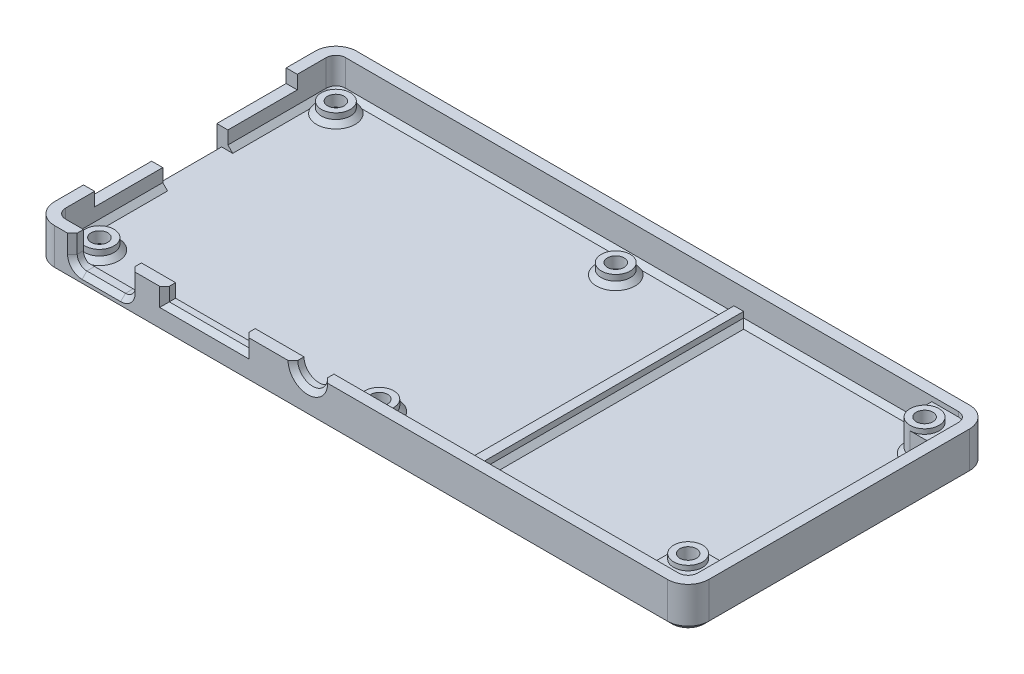
SolidWorks part; units mm, degrees
ref_plane "Front Plane" through (0, 0, 0) normal (0, 0, 1) x (1, 0, 0)
ref_plane "Top Plane" through (0, 0, 0) normal (0, 1, 0) x (1, 0, 0)
ref_plane "Right Plane" through (0, 0, 0) normal (1, 0, 0) x (0, 0, -1)
sketch "Sketch1" plane through (0, 0, 0) normal (0, 1, 0) x (1, 0, 0)
  line L0 (-71.5618, 3.106) -> (57.4382, 3.106) construction
  line L1 (-71.5618, 31.106) -> (57.4382, 31.106)
  line L2 (-71.5618, 31.106) -> (-71.5618, -24.894)
  line L3 (-71.5618, -24.894) -> (57.4382, -24.894)
  line L4 (57.4382, 31.106) -> (57.4382, -24.894)
  line L5 (-60.6618, -24.894) -> (-60.6618, -31.6828) construction
  line L6 (-68.0618, 27.606) -> (-10.0618, 27.606)
  line L7 (-68.0618, 27.606) -> (-68.0618, -21.394)
  line L8 (-68.0618, -21.394) -> (-10.0618, -21.394)
  line L9 (-10.0618, 27.606) -> (-10.0618, -21.394)
  line L10 (-39.5618, -24.894) -> (-39.5618, -31.6828) construction
  line L11 (-18.0618, -24.894) -> (-18.0618, -31.6828) construction
  line L12 (-65.4118, -26.5648) -> (-55.9118, -26.5648) construction
  line L13 (-48.0618, -26.5648) -> (-31.0618, -26.5648) construction
  line L14 (-22.0618, -26.5648) -> (-14.0618, -26.5648) construction
  line L15 (-72.5618, 9.606) -> (-72.5618, -3.394) construction
  line L16 (-71.5618, 3.106) -> (-72.5618, 3.106) construction
  dimension "D1" = 129
  dimension "D2" = 56
  dimension "D3" = 49
  dimension "D4" = 58
  dimension "D5" = 3.5
  dimension "D6" = 3.5
  dimension "D7" = 10.9
  dimension "D8" = 32
  dimension "D9" = 53.5
  dimension "D10" = 2
  dimension "D11" = 13
  dimension "D12" = 9.5
  dimension "D13" = 17
  dimension "D14" = 8
sketch "Sketch3" plane through (0, 0, 0) normal (0, 1, 0) x (1, 0, 0)
  line L4 (60.7382, 34.406) -> (-74.8618, 34.406)
  line L5 (-74.8618, 34.406) -> (-74.8618, -28.194)
  line L6 (-74.8618, -28.194) -> (60.7382, -28.194)
  line L7 (60.7382, -28.194) -> (60.7382, 34.406)
  line L8 (58.4382, 32.106) -> (-72.5618, 32.106)
  line L9 (58.4382, -25.894) -> (58.4382, 32.106)
  line L10 (-72.5618, -25.894) -> (58.4382, -25.894)
  line L11 (-72.5618, 32.106) -> (-72.5618, -25.894)
  line L12 (58.4382, 32.106) -> (-72.5618, 32.106)
  line L13 (58.4382, -25.894) -> (58.4382, 32.106)
  line L14 (-72.5618, -25.894) -> (58.4382, -25.894)
  line L15 (-72.5618, 32.106) -> (-72.5618, -25.894)
  line L16 (-7.0618, 3.106) -> (-7.0618, 34.406) construction
  line L17 (-71.5618, 3.106) -> (57.4382, 3.106) construction
  line L20 (-74.8618, 3.106) -> (52.7382, 3.106) construction
  line L25 (60.7382, -28.194) -> (60.7382, 34.406) construction
  line L26 (58.4382, -25.894) -> (58.4382, 32.106) construction
  dimension "D1" = 1
  dimension "D2" = 2.3
extrude "Boss-Extrude1" add sketch "Sketch3" along normal blind 8.5
sketch "Sketch5" plane through (0, 0, 0) normal (0, 1, 0) x (1, 0, 0)
  line L1 (-72.5618, 32.106) -> (58.4382, 32.106)
  line L2 (-72.5618, 32.106) -> (-72.5618, -25.894)
  line L3 (-72.5618, -25.894) -> (58.4382, -25.894)
  line L4 (58.4382, 32.106) -> (58.4382, -25.894)
extrude "Boss-Extrude2" add sketch "Sketch5" along normal blind 2
sketch "Sketch6" plane through (0, 2, 0) normal (0, 1, 0) x (1, 0, 0)
  circle A0 centre (-68.0618, 27.606) radius 3
  circle A1 centre (-68.0618, -21.394) radius 3
  circle A2 centre (-10.0618, -21.394) radius 3
  circle A3 centre (-10.0618, 27.606) radius 3
extrude "Boss-Extrude3" add sketch "Sketch6" along normal blind 2.2
sketch "Sketch10" plane through (0, 2, 0) normal (0, 1, 0) x (1, 0, 0)
  line L0 (58.4382, 32.106) -> (-72.5618, 32.106) construction
  line L1 (9.9382, 32.106) -> (11.9382, 32.106)
  line L2 (9.9382, 32.106) -> (9.9382, -25.894)
  line L3 (9.9382, -25.894) -> (11.9382, -25.894)
  line L4 (11.9382, 32.106) -> (11.9382, -25.894)
  line L5 (-72.5618, -25.894) -> (58.4382, -25.894) construction
  line L6 (-10.0618, 27.606) -> (-10.0618, -21.394) construction
  dimension "D1" = 2
  dimension "D2" = 20
extrude "Boss-Extrude4" add sketch "Sketch10" along normal blind 2.2
sketch "Sketch11" plane through (0, 0, 28.194) normal (0, 0, 1) x (1, 0, 0)
  line L0 (-74.8618, 8.5) -> (-74.8618, 0) construction
  line L1 (-66.8618, 8.5) -> (-54.8618, 8.5)
  line L2 (-66.8618, 8.5) -> (-66.8618, 2.7)
  line L3 (-66.8618, 2.7) -> (-54.8618, 2.7)
  line L4 (-54.8618, 8.5) -> (-54.8618, 2.7)
  line L5 (-74.8618, 0) -> (60.7382, 0) construction
  line L6 (-60.8618, 8.5) -> (-60.6618, 0) construction
  line L7 (-65.4118, 0) -> (-55.9118, 0) construction
  line L9 (-47.778, 8.5) -> (-31.278, 8.5)
  line L10 (-47.778, 8.5) -> (-47.778, 5.7)
  line L11 (-47.778, 5.7) -> (-31.278, 5.7)
  line L12 (-31.278, 8.5) -> (-31.278, 5.7)
  line L13 (-68.0618, 0) -> (-10.0618, 0) construction
  line L14 (-39.5618, 0) -> (-39.528, 8.5) construction
  line L15 (-48.0618, 0) -> (-31.0618, 0) construction
  line L16 (-18.0618, 0) -> (-18.0618, 8.5) construction
  line L17 (-22.0618, 0) -> (-14.0618, 0) construction
  line L18 (-74.8618, 8.5) -> (60.7382, 8.5) construction
  circle A0 centre (-18.0618, 8.5) radius 3.1
  dimension "D5" = 6.2
  dimension "D1" = 2.7
  dimension "D2" = 12
  dimension "D3" = 5.7
  dimension "D4" = 16.5
  dimension "D6" = 8
  dimension "D7" = 5.8
  dimension "D8" = 2.8
extrude "Cut-Extrude1" cut sketch "Sketch11" against normal up to next
sketch "Sketch12" plane through (-74.8618, 0, 0) normal (-1, 0, 0) x (0, 0, 1)
  line L0 (-3.106, 0) -> (-3.106, 8.5) construction
  line L1 (-27.606, 0) -> (21.394, 0) construction
  line L2 (-34.406, 8.5) -> (28.194, 8.5) construction
  line L3 (-24.106, 5.7) -> (17.894, 5.7)
  line L4 (-9.7329, 5.7) -> (3.7671, 5.7)
  line L5 (-9.7329, 5.7) -> (-9.7329, 2)
  line L6 (-9.7329, 2) -> (3.7671, 2)
  line L7 (3.7671, 5.7) -> (3.7671, 2)
  line L8 (-24.106, 8.5) -> (17.894, 8.5)
  line L9 (-24.106, 8.5) -> (-24.106, 5.7)
  line L11 (17.894, 8.5) -> (17.894, 5.7)
  line L12 (-9.7329, 3.85) -> (3.7671, 3.85) construction
  point P17 (-3.106, 5.7)
  dimension "D1" = 13.5
  dimension "D2" = 2.8
  dimension "D3" = 3.7
  dimension "D4" = 6.5
extrude "Cut-Extrude2" cut sketch "Sketch12" against normal up to next contours L9 L3 L11 L8 | L7 L6 L5 L4
fillet "Fillet6" radius 2 1 edges at (58.4382, 5.25, -32.106)
fillet "Fillet8" radius 2 2 edges at (-72.5618, 5.25, 25.894) (-72.5618, 5.25, -32.106)
chamfer "Chamfer1" distance 1 angle 45 4 edges at (-68.0618, 2, 24.394) (-10.0618, 2, 24.394) (-10.0618, 2, -24.606) (-68.0618, 2, -24.606)
sketch "Sketch24" plane through (0, 2, 0) normal (0, 1, 0) x (1, 0, 0)
  line L0 (11.9382, 3.106) -> (61.5789, 3.106) construction
  line L1 (11.9382, -25.894) -> (11.9382, 32.106) construction
  line L2 (53.9382, -18.394) -> (58.4382, -18.394)
  line L3 (58.4382, -25.894) -> (58.4382, 30.106) construction
  line L4 (-68.0618, 27.606) -> (-10.0618, 27.606) construction
  line L5 (-68.0618, 27.606) -> (-68.0618, -21.394) construction
  line L6 (-68.0618, -21.394) -> (-10.0618, -21.394) construction
  line L7 (-10.0618, 27.606) -> (-10.0618, -21.394) construction
  line L8 (-10.0618, 27.606) -> (53.9382, 27.606) construction
  line L9 (-10.0618, 27.606) -> (-10.0618, -21.394) construction
  line L10 (-10.0618, -21.394) -> (53.9382, -21.394) construction
  line L11 (53.9382, 27.606) -> (53.9382, -21.394) construction
  line L12 (50.9382, -21.394) -> (50.9382, -25.894)
  line L13 (11.9382, -25.894) -> (58.4382, -25.894) construction
  line L14 (58.4382, -25.894) -> (58.4382, 30.106) construction
  line L15 (58.4382, -18.394) -> (58.4382, -25.894)
  line L16 (58.4382, -25.894) -> (50.9382, -25.894)
  line L17 (50.9382, 27.606) -> (50.9382, 32.106)
  line L18 (56.4382, 32.106) -> (-70.5618, 32.106) construction
  line L19 (53.9382, 24.606) -> (58.4382, 24.606)
  line L20 (58.4382, 24.606) -> (58.4382, 32.106)
  line L21 (58.4382, 32.106) -> (50.9382, 32.106)
  arc A0 (50.9382, -21.394) -> (53.9382, -18.394) centre (53.9382, -21.394) cw
  arc A1 (50.9382, 27.606) -> (53.9382, 24.606) centre (53.9382, 27.606) ccw
  dimension "D2" = 4.5
extrude "Boss-Extrude7" add sketch "Sketch24" along normal up to surface (6.5 mm away) up to face at (-8.3784, 8.5, -11.175)
fillet "Fillet20" radius 4.3 4 edges at (60.7382, 4.25, 28.194) (-74.8618, 4.25, -34.406) (-74.8618, 4.25, 28.194) (60.7382, 4.25, -34.406)
chamfer "Chamfer5" distance 1 angle 45 17 edges at (-72.5618, 2, 13.8305) (-72.5618, 2, -19.9195) (-71.976, 2, 25.3082) (-71.976, 2, -31.5202) (-30.3118, 2, 25.894) (-30.3118, 2, -32.106) (9.9382, 2, -3.106) (11.9382, 2, -3.106) (31.4382, 2, -32.106) (31.4382, 2, 25.894) (51.8169, 2, 19.2727) (58.4382, 2, -3.106) (51.8169, 2, -25.4847) (50.9382, 2, -29.856) (56.1882, 2, -24.606) (56.1882, 2, 18.394) (50.9382, 2, 23.644)
hole_wizard "CSK for #4 Flat Head Socket Cap Screw1" positions "Sketch28" profile "Sketch27" countersink size "#4" standard "ANSI Inch"
sketch "Sketch28" plane through (0, 0, 0) normal (0, -1, 0) x (-1, 0, 0)
  point P0 (68.0618, 27.606)
  point P4 (68.0618, -21.394)
  point P8 (-53.9382, 27.606)
  point P12 (-53.9382, -21.394)
  point P15 (10.0618, -21.394)
  point P19 (10.0618, 27.606)
sketch "Sketch27" plane through (-68.0618, 0, -27.606) normal (1, 0, 0) x (0, 0, -1)
  line L0 (0, 0) -> (0, 15.0378)
  line L1 (0, 15.0378) -> (1.7272, 14)
  line L2 (1.7272, 14) -> (1.7272, 1.8805)
  line L3 (1.7272, 1.8805) -> (3.3619, 0)
  line L5 (3.3619, 0) -> (0, 0)
  line L6 (-1.7272, 1.8805) -> (-3.3619, 0) construction
  line L10 (0, 15.0378) -> (-1.7272, 14) construction
  line L11 (0, -6.35) -> (0, 107.95) construction
  dimension "Hole Dia." = 3.4544
  dimension "Hole Depth" = 14
  dimension "Near C'Sink Dia." = 6.7238
  dimension "Near C'Sink Angle" = 82
  dimension "Drill Angle" = 118
chamfer "Chamfer7" distance 1 angle 45 8 edges at (-74.8618, 0, -3.106) (-73.6023, 0, 26.9346) (-73.6023, 0, -33.1466) (-7.0618, 0, 28.194) (-7.0618, 0, -34.406) (59.4788, 0, 26.9346) (59.4788, 0, -33.1466) (60.7382, 0, -3.106)
chamfer "Chamfer8" distance 1 angle 45 1 edges at (-74.8618, 2, -2.9829)
sketch "Sketch29" plane through (0, 8.5, 0) normal (0, 1, 0) x (1, 0, 0)
  line L0 (53.9382, 24.606) -> (58.4382, 24.606)
  line L1 (58.4382, 24.606) -> (58.4382, 30.106)
  line L2 (56.4382, 32.106) -> (50.9382, 32.106)
  line L3 (50.9382, 32.106) -> (50.9382, 27.606)
  line L4 (53.9382, -18.394) -> (58.4382, -18.394)
  line L5 (58.4382, -18.394) -> (58.4382, -23.894)
  line L6 (56.4382, -25.894) -> (50.9382, -25.894)
  line L7 (50.9382, -25.894) -> (50.9382, -21.394)
  arc A0 (53.9382, 24.606) -> (50.9382, 27.606) centre (53.9382, 27.606) ccw
  arc A1 (56.4382, 32.106) -> (58.4382, 30.106) centre (56.4382, 30.106) cw
  arc A2 (50.9382, -21.394) -> (53.9382, -18.394) centre (53.9382, -21.394) ccw
  arc A3 (56.4382, -25.894) -> (58.4382, -23.894) centre (56.4382, -23.894) ccw
extrude "Cut-Extrude3" cut sketch "Sketch29" against normal blind 1
fillet "Fillet21" radius 2 2 edges at (-54.8618, 2.7, 26.894) (-66.8618, 2.7, 26.894)
chamfer "Chamfer9" distance 1 angle 45 9 edges at (-18.0618, 5.4, 28.194) (-31.278, 7.1, 28.194) (-39.528, 5.7, 28.194) (-47.778, 7.1, 28.194) (-54.8618, 6.6, 28.194) (-55.4476, 3.2858, 28.194) (-60.8618, 2.7, 28.194) (-66.276, 3.2858, 28.194) (-66.8618, 6.6, 28.194)
